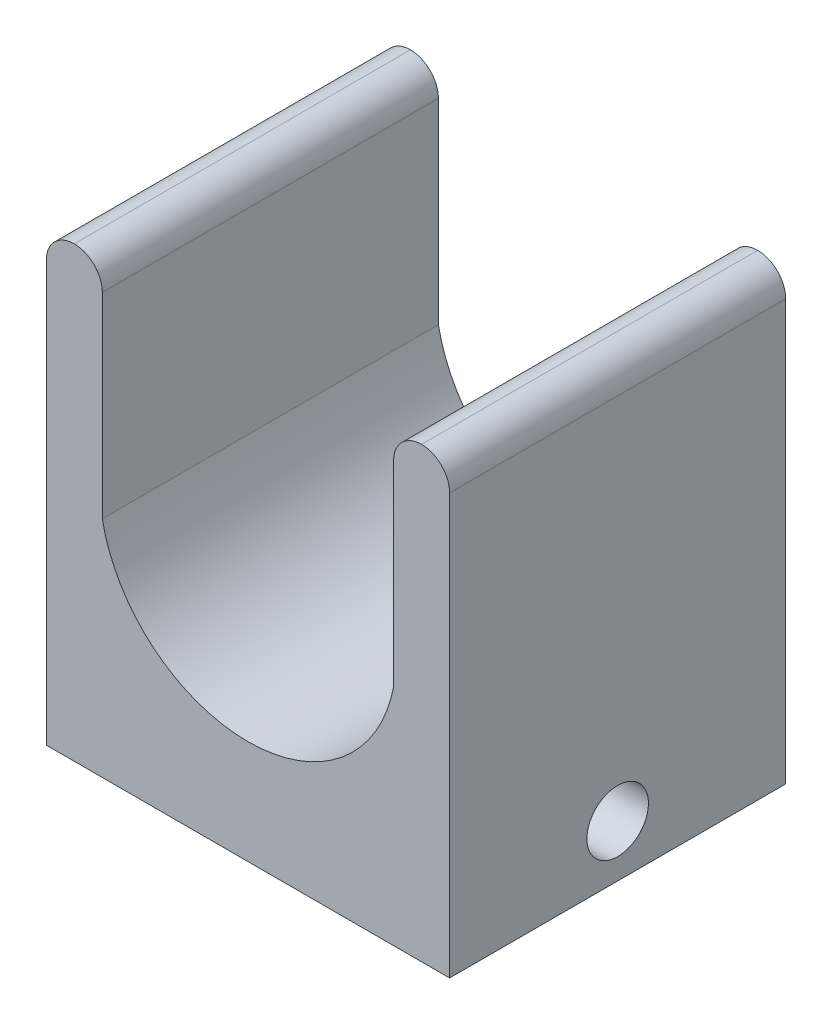
SolidWorks part; units mm, degrees
ref_plane "Front Plane" through (0, 0, 0) normal (0, 0, 1) x (1, 0, 0)
ref_plane "Top Plane" through (0, 0, 0) normal (0, 1, 0) x (1, 0, 0)
ref_plane "Right Plane" through (0, 0, 0) normal (1, 0, 0) x (0, 0, -1)
sketch "Sketch2" plane through (0, 0, 0) normal (0, 0, 1) x (1, 0, 0)
  line L0 (0, -19.7944) -> (0, -15.7944) construction
  line L1 (-26, 45.6658) -> (0, 45.6658) construction
  line L2 (0, 45.6658) -> (26, 45.6658) construction
  line L3 (-26, 45.6658) -> (-26, 5.6658)
  line L4 (26, 45.6658) -> (26, 5.6658)
  line L5 (-26, 45.6658) -> (-36, 45.6658)
  line L6 (-36, 45.6658) -> (-36, 5.6658)
  line L7 (26, 45.6658) -> (36, 45.6658)
  line L8 (36, 45.6658) -> (36, 2.6428)
  line L9 (-36, 5.6658) -> (-36, -34.3342)
  line L10 (-36, -34.3342) -> (36, -34.3342)
  line L11 (36, -34.3342) -> (36, 2.6428)
  line L12 (0, -15.7944) -> (0, -34.3342) construction
  line L13 (0, -15.7944) -> (0, -34.3342) construction
  arc A0 (-26, 5.6658) -> (26, 5.6658) centre (0, 10.6858) ccw
  dimension "D1" = 52
  dimension "D2" = 40
  dimension "D3" = 40
  dimension "D4" = 40
  dimension "D5" = 10
  dimension "D6" = 4
extrude "Boss-Extrude1" add sketch "Sketch2" along normal blind 60
fillet "Fillet2" radius 5 4 edges at (36, 45.6658, 30) (26, 45.6658, 30) (-26, 45.6658, 30) (-36, 45.6658, 30)
sketch "Sketch4" plane through (0, 0, 60) normal (0, 0, 1) x (1, 0, 0)
  line L0 (0, -15.7944) -> (0, -34.3342) construction
  line L1 (-36, -34.3342) -> (36, -34.3342) construction
  line L2 (0, -25.0643) -> (36, -25.0643) construction
  line L3 (36, -34.3342) -> (36, 40.6658) construction
  arc A0 (-26, 5.6658) -> (26, 5.6658) centre (0, 10.6858) ccw construction
sketch "Sketch5" plane through (36, 0, 0) normal (1, 0, 0) x (0, 0, -1)
  line L0 (-60, -25.0643) -> (0, -25.0643) construction
  line L1 (-60, -15.7944) -> (-60, -34.3342) construction
  line L2 (0, -34.3342) -> (0, 40.6658) construction
  circle A0 centre (-30, -25.0643) radius 5.5
  dimension "D1" = 11
extrude "Cut-Extrude1" cut sketch "Sketch5" against normal through all
